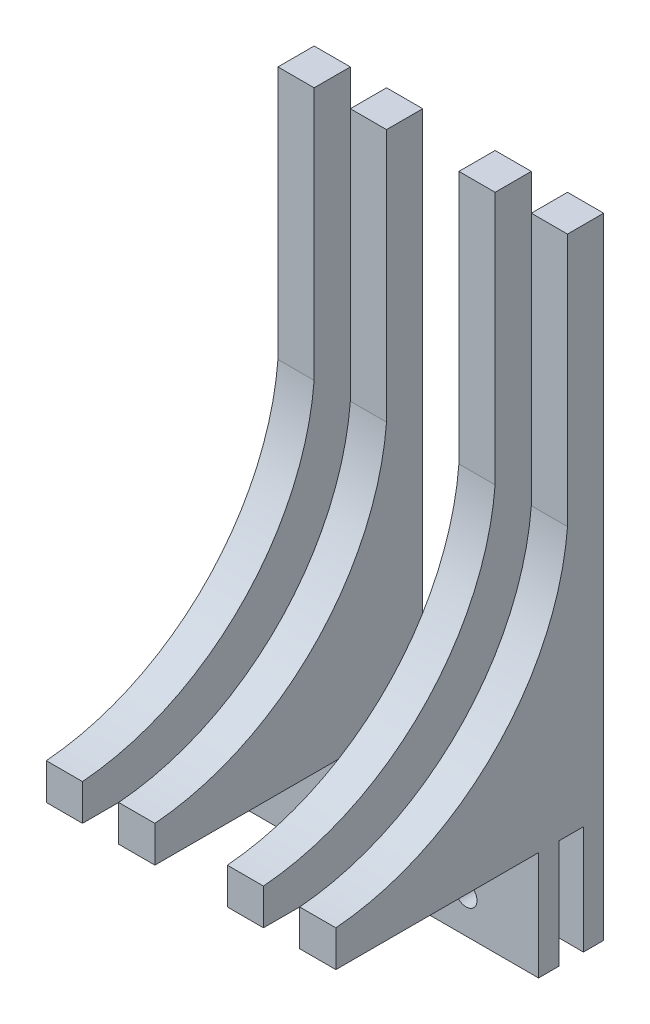
SolidWorks part; units mm, degrees
ref_plane "Front Plane" through (0, 0, 0) normal (0, 0, 1) x (1, 0, 0)
ref_plane "Top Plane" through (0, 0, 0) normal (0, 1, 0) x (1, 0, 0)
ref_plane "Right Plane" through (0, 0, 0) normal (1, 0, 0) x (0, 0, -1)
sketch "Sketch1" plane through (0, 0, 0) normal (1, 0, 0) x (0, 0, -1)
  line L0 (0, 0) -> (0, 23)
  line L1 (0, 23) -> (9, 23)
  line L2 (9, 23) -> (9, 0)
  line L8 (0, 0) -> (9, 0)
  dimension "D2" = 9
  dimension "D4" = 23
extrude "Boss-Extrude1" add sketch "Sketch1" along normal blind 40
ref_plane "Plane1" through (20, 0, 0) normal (-1, 0, 0) x (0, 0, 1)
sketch "Sketch3" plane through (0, 0, 0) normal (-1, 0, 0) x (0, 0, 1)
  line L0 (0, 0) -> (28, 0)
  line L1 (-9, 23) -> (-9, 37)
  line L3 (28, 0) -> (28, 5)
  line L5 (-9, 23) -> (0, 23)
  line L6 (-9, 37) -> (-9, 72)
  line L7 (0, 0) -> (0, 23)
  line L8 (-9, 72) -> (-4, 72)
  line L9 (-4, 72) -> (-4, 37)
  arc A0 (-4, 37) -> (28, 5) centre (30.8812, 39.8812) ccw
  dimension "D1" = 35
  dimension "D2" = 37
  dimension "D3" = 37
  dimension "D4" = 5
  dimension "D5" = 5
  dimension "D6" = 35
  dimension "D7" = 5
extrude "Boss-Extrude2" add sketch "Sketch3" against normal blind 5
pattern_linear "LPattern1" count 2 spacing 10 along (1, 0, 0) of "Boss-Extrude2"
sketch "Sketch6" plane through (0, 0, 0) normal (0, -1, 0) x (1, 0, 0)
  line L0 (40, 0) -> (40, -9) construction
  line L1 (0, -9) -> (40, -9)
  line L2 (0, -9) -> (0, -6.2)
  line L3 (0, -6.2) -> (40, -6.2)
  line L4 (40, -9) -> (40, -6.2)
  line L5 (0, 28) -> (0, -9) construction
  line L6 (40, 0) -> (0, 0)
  line L7 (40, 0) -> (40, -2.8)
  line L8 (40, -2.8) -> (0, -2.8)
  line L9 (0, 0) -> (0, -2.8)
  dimension "D1" = 3.4
extrude "Boss-Extrude4" add sketch "Sketch6" along normal blind 15
sketch "Sketch7" plane through (0, 0, 28) normal (0, 0, 1) x (1, 0, 0)
  line L0 (10, 37) -> (10, 5) construction
  line L1 (5, 0) -> (10, 0)
  line L2 (5, 0) -> (5, 23)
  line L3 (5, 23) -> (10, 23)
  line L4 (10, 0) -> (10, 23)
  line L5 (10, 23) -> (10, 0) construction
  line L6 (20, 4.95) -> (20, -4.95) construction
  line L7 (20, 23) -> (15, 23)
  line L8 (20, 23) -> (20, 0)
  line L9 (20, 0) -> (15, 0)
  line L10 (15, 23) -> (15, 0)
  line L11 (40, 23) -> (15, 23) construction
  line L12 (15, 23) -> (15, 0) construction
extrude "Cut-Extrude1" cut sketch "Sketch7" against normal through all
sketch "Sketch8" plane through (0, 0, 0) normal (0, 0, 1) x (1, 0, 0)
  line L2 (0, -15) -> (0, 0) construction
  line L3 (10, 0) -> (5, 0) construction
  circle A0 centre (10, -10) radius 1.5
  circle A3 centre (20, -10) radius 1.5
  circle A4 centre (30, -10) radius 1.5
  dimension "D1" = 3
  dimension "D2" = 10
  dimension "D3" = 10
  dimension "D4" = 3
  dimension "D5" = 10
extrude "Cut-Extrude2" cut sketch "Sketch8" against normal through all
mirror "Mirror1" about plane through (20, 0, 0) normal (-1, 0, 0) of "LPattern1", "Cut-Extrude1", "Boss-Extrude2"
